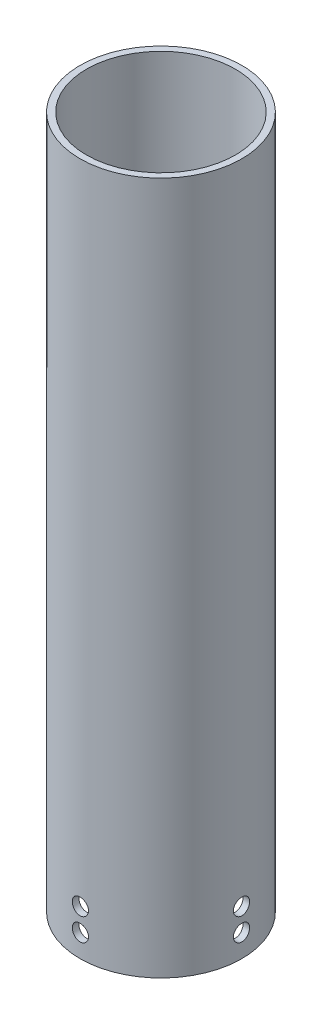
SolidWorks part; units mm, degrees
material "ПВХ 0.007 Смягченный"
ref_plane "Спереди" through (0, 0, 0) normal (0, 0, 1) x (1, 0, 0)
ref_plane "Сверху" through (0, 0, 0) normal (0, 1, 0) x (1, 0, 0)
ref_plane "Справа" through (0, 0, 0) normal (1, 0, 0) x (0, 0, -1)
sketch "Эскиз1" plane through (0, 0, 0) normal (0, 1, 0) x (1, 0, 0)
  circle A0 centre (0, 0) radius 25
  circle A1 centre (0, 0) radius 23
  dimension "ExDBody" = 50
  dimension "InDBody" = 46
extrude "Бобышка-Вытянуть1" add sketch "Эскиз1" along normal blind 214
sketch "Эскиз2" plane through (0, 0, 0) normal (0, 0, 1) x (1, 0, 0)
  line L0 (-25, 0) -> (-25, 20) construction
  line L1 (-25, 214) -> (-25, 0) construction
  line L2 (-25, 20) -> (41.185, 20) construction
  line L3 (-25, 7) -> (-25, 27) construction
  line L4 (-25, 0) -> (25, 0) construction
  circle A0 centre (0, 7) radius 2.5
  circle A1 centre (0, 14) radius 2.5
  dimension "D2" = 5
  dimension "D1" = 20
  dimension "D4" = 7
  dimension "D3" = 2
extrude "Вырез-Вытянуть1" cut sketch "Эскиз2" against normal through all and the other way through all
pattern_circular "Круговой массив1" count 2 over 90 about axis through (0, 214, 0) along (0, -1, 0) of "Вырез-Вытянуть1" reverse direction yes
